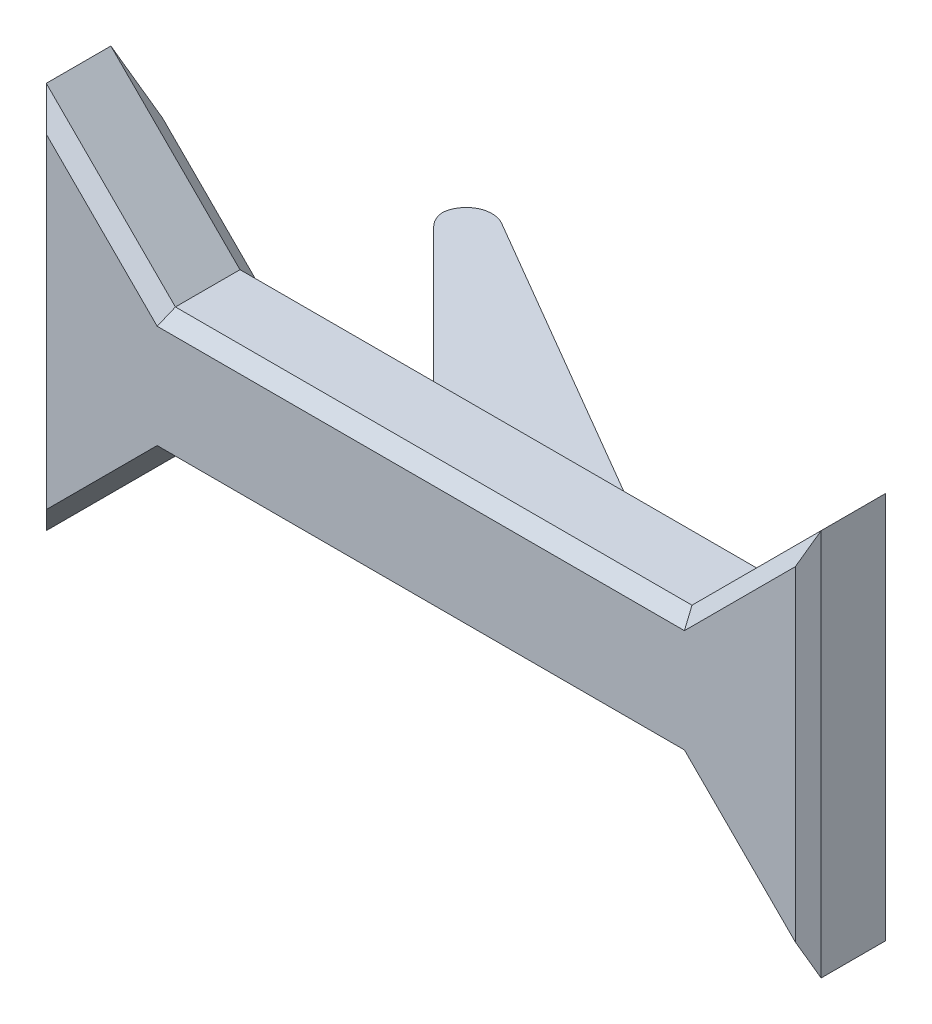
SolidWorks part; units mm, degrees
ref_plane "Front Plane" through (0, 0, 0) normal (0, 0, 1) x (1, 0, 0)
ref_plane "Top Plane" through (0, 0, 0) normal (0, 1, 0) x (1, 0, 0)
ref_plane "Right Plane" through (0, 0, 0) normal (1, 0, 0) x (0, 0, -1)
sketch "Sketch1" plane through (0, 0, 0) normal (0, 0, 1) x (1, 0, 0)
  line L0 (-10, 2.5) -> (-15, 7.5)
  line L1 (-10, -2.5) -> (10, -2.5)
  line L2 (-10, -2.5) -> (-10, 2.5)
  line L3 (-10, 2.5) -> (10, 2.5)
  line L4 (10, -2.5) -> (10, 2.5)
  line L5 (-10, -2.5) -> (10, 2.5) construction
  line L6 (-10, 2.5) -> (10, -2.5) construction
  line L7 (-15, 7.5) -> (-15, -7.5)
  line L8 (-15, -7.5) -> (-10, -2.5)
  line L9 (0, 0) -> (0, 2.5) construction
  line L10 (15, -7.5) -> (10, -2.5)
  line L11 (15, 7.5) -> (15, -7.5)
  line L12 (10, 2.5) -> (15, 7.5)
  point P0 (0, 0)
  point P6 (-15, 0)
  dimension "D1" = 20
  dimension "D2" = 5
  dimension "D3" = 5
  dimension "D4" = 135
extrude "Boss-Extrude1" add sketch "Sketch1" along normal blind 4 contours L7 L8 L2 L0 | L1 L4 L3 L2 | L12 L4 L10 L11 region at (-12.9167, 0, 0) region at (0, 0, 0) region at (12.9167, 0, 0)
sketch "Sketch4" plane through (0, 0, 0) normal (0, 1, 0) x (1, 0, 0)
  line L0 (3.5, 0) -> (-8.5, 7)
  line L1 (-10, 0) -> (10, 0) construction
  line L2 (-8.5, 7) -> (-8.5, 5)
  line L3 (-8.5, 5) -> (-3.5, 0)
  line L4 (-3.5, 0) -> (3.5, 0) construction
  line L9 (10, 0) -> (-10, 0)
  line L10 (-10, 0) -> (-10, -4)
  line L11 (-10, -4) -> (10, -4)
  line L12 (10, -4) -> (10, 0)
  line L13 (3.5, 0) -> (-3.5, 0)
  point P4 (4.6214, 0)
  point P7 (0, 0)
  dimension "D1" = 45
  dimension "D2" = 7
  dimension "D3" = 5
  dimension "D4" = 7
  dimension "D5" = 0
extrude "Boss-Extrude2" add sketch "Sketch4" along normal mid plane 4 contours L0 L2 L3 L13
chamfer "Chamfer1" distance 0.5 angle 45 8 edges at (-12.5, 5, 4) (0, 2.5, 4) (12.5, 5, 4) (15, 0, 4) (12.5, -5, 4) (0, -2.5, 4) (-12.5, -5, 4) (-15, 0, 4)
chamfer "Chamfer2" distance 1 angle 45 8 edges at (12.5, -5, 0) (15, 0, 0) (12.5, 5, 0) (0, 2.5, 0) (0, -2.5, 0) (-12.5, -5, 0) (-12.5, 5, 0) (-15, 0, 0)
chamfer "Chamfer3" distance 1 angle 45 1 edges at (-3.5, 0, 0) first distance on face at (-5, 0, -1.5)
fillet "Fillet5" radius 1 2 edges at (-8.5, 0, -7) (-8.5, 0, -5)
